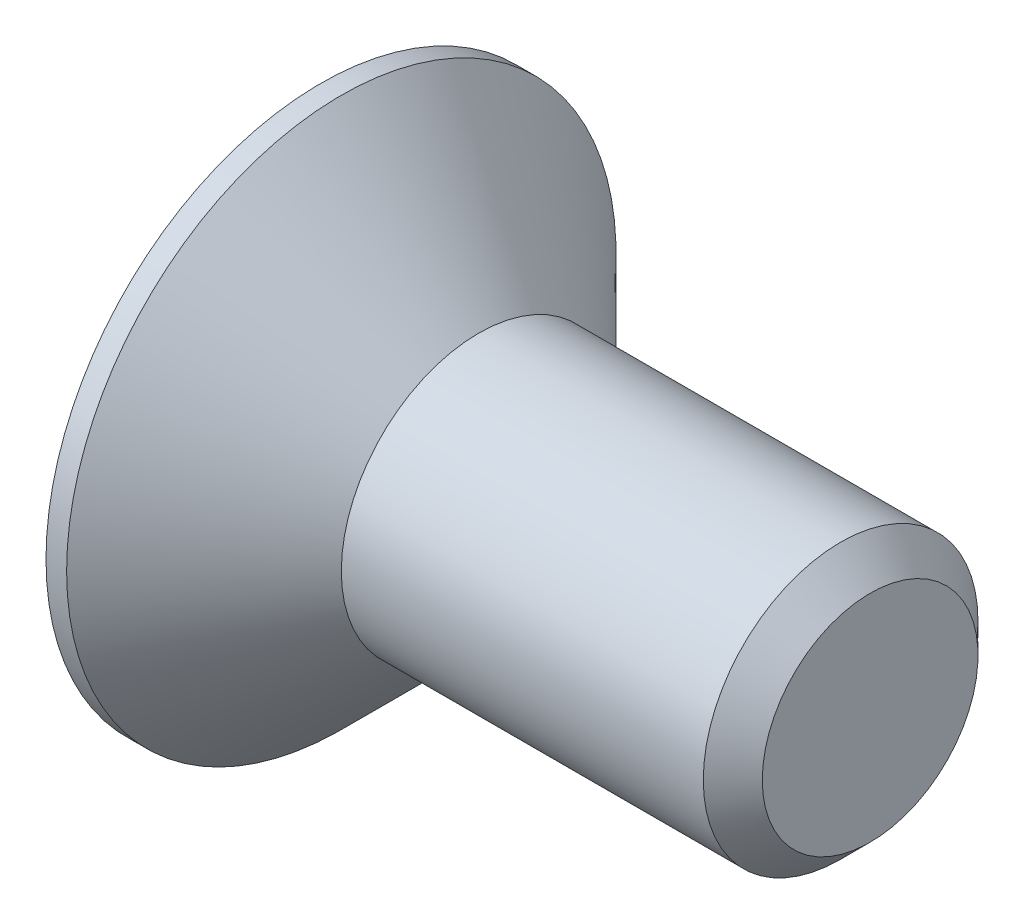
SolidWorks part; units mm, degrees
ref_plane "Płaszczyzna przednia" through (0, 0, 0) normal (0, 0, 1) x (1, 0, 0)
ref_plane "Płaszczyzna górna" through (0, 0, 0) normal (0, 1, 0) x (1, 0, 0)
ref_plane "Płaszczyzna prawa" through (0, 0, 0) normal (1, 0, 0) x (0, 0, -1)
sketch "Szkic1" plane through (0, 0, 0) normal (0, 0, 1) x (1, 0, 0)
  line L0 (0, 0) -> (0, 4)
  line L1 (0, 4) -> (0.3, 4)
  line L2 (0.3, 4) -> (2.3, 2)
  line L3 (2.3, 2) -> (2.3, 0)
  line L4 (2.3, 0) -> (0, 0)
  line L5 (2.3, 0) -> (0, 0) construction
revolve "Obrót1" add sketch "Szkic1" angle 360 about L5 reverse direction yes
sketch "Szkic2" plane through (0, 0, 0) normal (0, 0, 1) x (1, 0, 0)
  line L0 (2.3, 0) -> (2.3, 2)
  line L1 (2.3, 2) -> (7.5705, 2)
  line L2 (7.5705, 2) -> (8, 1.5705)
  line L3 (8, 1.5705) -> (8, 0)
  line L4 (8, 0) -> (2.3, 0)
  line L5 (8, 0) -> (2.3, 0) construction
revolve "Obrót2" add sketch "Szkic2" angle 360 about L5 reverse direction yes
cosmetic thread "Oznaczenie gwintu1" parameters "D1"=4.7, "D2"=3.141
sketch "Szkic3" plane through (0, 0, 0) normal (0, 0, 1) x (1, 0, 0)
  line L0 (0, 0) -> (0, 1.95)
  line L1 (0, 1.95) -> (1.5, 1.95)
  line L2 (1.5, 1.95) -> (2.6258, 0)
  line L3 (2.6258, 0) -> (0, 0)
  line L4 (2.6258, 0) -> (0, 0) construction
revolve "Wycięcie-obrót1" cut sketch "Szkic3" angle 360 about L4 reverse direction yes
sketch "Szkic4" plane through (0, 0, 0) normal (1, 0, 0) x (0, 0, -1)
  line L0 (-1.25, 0.7217) -> (-1.25, -0.7217)
  line L1 (-1.25, -0.7217) -> (0, -1.4434)
  line L2 (0, -1.4434) -> (1.25, -0.7217)
  line L3 (1.25, -0.7217) -> (1.25, 0.7217)
  line L4 (1.25, 0.7217) -> (0, 1.4434)
  line L5 (0, 1.4434) -> (-1.25, 0.7217)
  circle A0 centre (0, 0) radius 2.25
extrude "Dodanie-wyciągnięcie1" add sketch "Szkic4" along normal blind 1.875
ref_plane "Płaszczyzna1" through (2.3, 0, 0) normal (1, 0, 0) x (0, 0, -1)
ref_plane "Płaszczyzna2" through (8, 0, 0) normal (1, 0, 0) x (0, 0, -1)
ref_plane "IP1 XY" through (0, 0, 0) normal (1, 0, 0) x (0, 0, -1)
ref_plane "IP1 XZ" through (0, 0, 0) normal (0, -1, 0) x (-1, 0, 0)
ref_plane "IP1 YZ" through (0, 0, 0) normal (0, 0, -1) x (-1, 0, 0)
ref_axis "IP1 X" through (0, 0, 80.9) along (0, 0, -1)
ref_axis "IP1 Y" through (0, -50, 0) along (0, 1, 0)
ref_axis "IP1 Z" through (80.9, 0, 0) along (-1, 0, 0)
sketch3d "IP1"
  point P0 (0, 0, 0)
ref_plane "IP2 XY" through (2.3, 0, 0) normal (1, 0, 0) x (0, 0, -1)
ref_plane "IP2 XZ" through (0, 0, 0) normal (0, -1, 0) x (-1, 0, 0)
ref_plane "IP2 YZ" through (0, 0, 0) normal (0, 0, -1) x (-1, 0, 0)
ref_axis "IP2 X" through (2.3, 0, 80.9) along (0, 0, -1)
ref_axis "IP2 Y" through (2.3, -50, 0) along (0, 1, 0)
ref_axis "IP2 Z" through (80.9, 0, 0) along (-1, 0, 0)
sketch3d "IP2"
  point P0 (2.3, 0, 0)
ref_plane "IP3 XY" through (8, 0, 0) normal (1, 0, 0) x (0, 0, -1)
ref_plane "IP3 XZ" through (0, 0, 0) normal (0, -1, 0) x (-1, 0, 0)
ref_plane "IP3 YZ" through (0, 0, 0) normal (0, 0, -1) x (-1, 0, 0)
ref_axis "IP3 X" through (8, 0, 80.9) along (0, 0, -1)
ref_axis "IP3 Y" through (8, -50, 0) along (0, 1, 0)
ref_axis "IP3 Z" through (80.9, 0, 0) along (-1, 0, 0)
sketch3d "IP3"
  point P0 (8, 0, 0)
